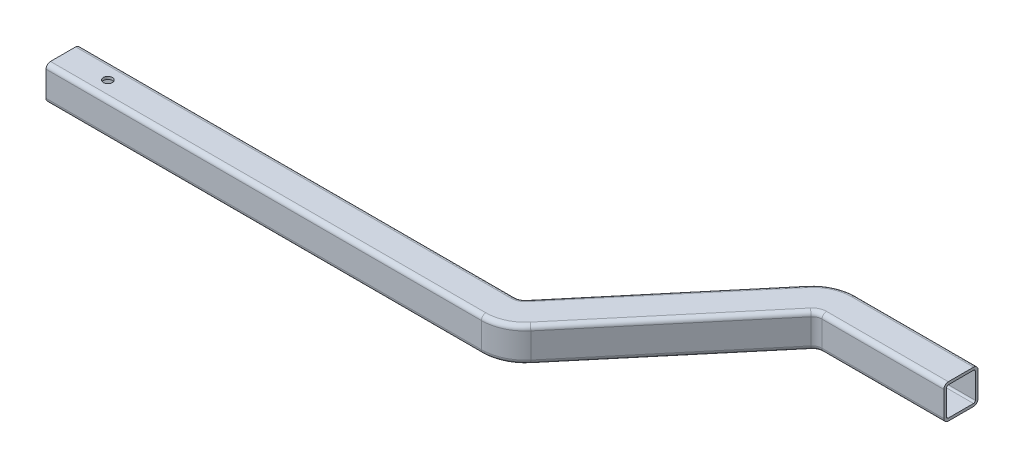
SolidWorks part; units mm, degrees
material "5052-H38, Rod (SS)"
ref_plane "Front Plane" through (0, 0, 0) normal (0, 0, 1) x (1, 0, 0)
ref_plane "Top Plane" through (0, 0, 0) normal (0, 1, 0) x (1, 0, 0)
ref_plane "Right Plane" through (0, 0, 0) normal (1, 0, 0) x (0, 0, -1)
sketch "Sketch2" plane through (0, 0, 0) normal (1, 0, 0) x (0, 0, -1)
  line L1 (-14.05, -19.05) -> (14.05, -19.05)
  line L2 (-19.05, -14.05) -> (-19.05, 14.05)
  line L3 (-14.05, 19.05) -> (14.05, 19.05)
  line L4 (19.05, -14.05) -> (19.05, 14.05)
  line L5 (-19.05, -19.05) -> (19.05, 19.05) construction
  line L6 (-19.05, 19.05) -> (19.05, -19.05) construction
  arc A0 (19.05, -14.05) -> (14.05, -19.05) centre (14.05, -14.05) cw
  arc A1 (-14.05, -19.05) -> (-19.05, -14.05) centre (-14.05, -14.05) cw
  arc A2 (-19.05, 14.05) -> (-14.05, 19.05) centre (-14.05, 14.05) cw
  arc A3 (14.05, 19.05) -> (19.05, 14.05) centre (14.05, 14.05) cw
  point P0 (0, 0)
  dimension "D3" = 5
  dimension "D1" = 38.1
  dimension "D2" = 38.1
sketch3d "3DSketch2"
  line L0 (508.9921, 0, -10.7164) -> (651.7048, 0, -180.7947)
  line L1 (674.6861, 0, -191.5111) -> (810.6969, 0, -191.5111)
  line L3 (0, 0, 0) -> (486.0108, 0, 0)
  line L4 (500, 0, 0) -> (628.2254, 0, 0) construction
  arc A0 (651.7048, 0, -180.7947) -> (674.6861, 0, -191.5111) centre (674.6861, 0, -161.5111) ccw
  arc A1 (486.0108, 0, 0) -> (508.9921, 0, -10.7164) centre (486.0108, 0, -30) ccw
  point P9 (660.6969, 0, -191.5111)
  point P10 (674.6861, -30, -161.5111)
  point P13 (500, 0, 0)
  point P15 (486.0108, 30, -30)
  dimension "D5" = 30
  dimension "D6" = 30
  dimension "D1" = 500
  dimension "D2" = 250
  dimension "D3" = 130
  dimension "D4" = 150
sweep "Sweep-Thin3" add profiles "Sketch2" path "3DSketch2" parameters "D1"=3
sketch "Sketch21" plane through (0, 0, 0) normal (0, 1, 0) x (1, 0, 0)
  line L0 (0, 0) -> (486.0108, 0) construction
  circle A0 centre (50, 0) radius 5
  dimension "D1" = 10
  dimension "D2" = 50
extrude "Cut-Extrude3" cut sketch "Sketch21" against normal through all both and the other way through all
sketch "Sketch22" [suppressed] plane through (0, 0, 0) normal (0, 0, 1) x (1, 0, 0)
ref_plane "Plane1" [suppressed] through (0, -210, 0) normal (0, 1, 0) x (1, 0, 0)
